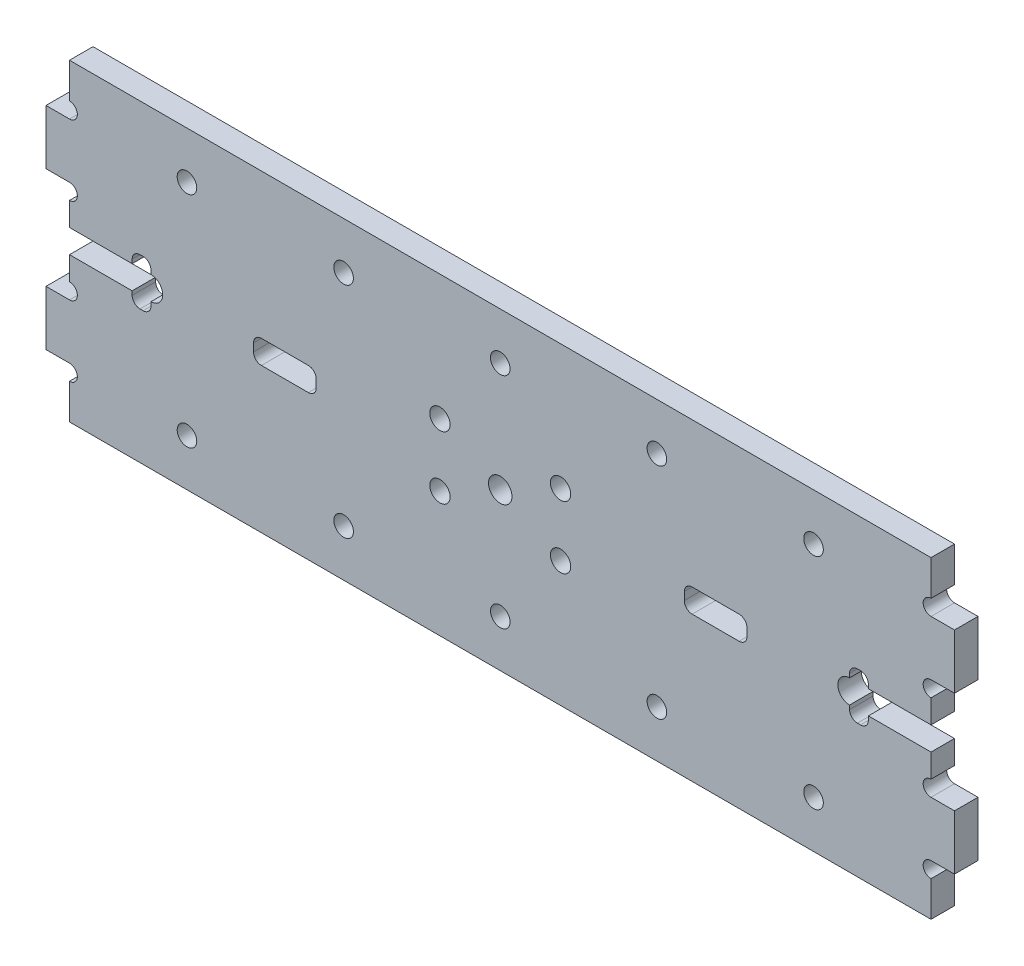
SolidWorks part; units mm, degrees
material "Acrylic (Medium-high impact)"
ref_plane "Front Plane" through (0, 0, 0) normal (0, 0, 1) x (1, 0, 0)
ref_plane "Top Plane" through (0, 0, 0) normal (0, 1, 0) x (1, 0, 0)
ref_plane "Right Plane" through (0, 0, 0) normal (1, 0, 0) x (0, 0, -1)
sketch "Sketch1" plane through (0, 0, 0) normal (0, 0, 1) x (1, 0, 0)
  line L0 (0, 20) -> (0, -20) construction
  line L1 (-55, 20) -> (55, 20)
  line L2 (-55, 20) -> (-55, -20)
  line L3 (-55, -20) -> (55, -20)
  line L4 (55, 20) -> (55, -20)
  line L5 (55, 0) -> (-55, 0) construction
  point P8 (0, 0)
extrude "Boss-Extrude1" add sketch "Sketch1" along normal blind 3
sketch "Sketch2" plane through (0, 0, 3) normal (0, 0, 1) x (1, 0, 0)
  line L0 (-55, 0) -> (55, 0) construction
  line L1 (-55, 20) -> (-55, -20) construction
  line L2 (55, -20) -> (55, 20) construction
  line L3 (55, 0) -> (55, -20) construction
  line L4 (55, 0) -> (55, 20) construction
  line L5 (55, 20) -> (58, 20) construction
  line L6 (58, 20) -> (58, -20) construction
  line L7 (58, -20) -> (55, -20) construction
  line L8 (0, 20) -> (0, -20) construction
  line L9 (55, 20) -> (-55, 20) construction
  line L10 (-55, -20) -> (55, -20) construction
  line L11 (55, -10) -> (58, -10) construction
  line L12 (55, 10) -> (58, 10) construction
  line L13 (58, 10) -> (58, 13.5)
  line L14 (58, 10) -> (58, 6.5)
  line L15 (58, 6.5) -> (55, 6.5)
  line L16 (55, 6.5) -> (55, 13.5)
  line L17 (55, 13.5) -> (58, 13.5)
  line L18 (55, -10) -> (55, -6.5)
  line L19 (55, -6.5) -> (58, -6.5)
  line L20 (58, -6.5) -> (58, -13.5)
  line L21 (58, -13.5) -> (55, -13.5)
  line L22 (55, -13.5) -> (55, -10)
  line L23 (-55, 6.5) -> (-55, 13.5)
  line L24 (-55, -13.5) -> (-55, -10)
  line L25 (-55, -10) -> (-55, -6.5)
  line L26 (-55, 10) -> (-58, 10) construction
  line L27 (-55, -10) -> (-58, -10) construction
  line L28 (-58, -20) -> (-55, -20) construction
  line L29 (-58, 20) -> (-58, -20) construction
  line L30 (-55, 20) -> (-58, 20) construction
  line L31 (-58, -13.5) -> (-55, -13.5)
  line L32 (-58, -6.5) -> (-58, -13.5)
  line L33 (-55, -6.5) -> (-58, -6.5)
  line L34 (-55, 13.5) -> (-58, 13.5)
  line L35 (-58, 6.5) -> (-55, 6.5)
  line L36 (-58, 10) -> (-58, 6.5)
  line L37 (-58, 10) -> (-58, 13.5)
extrude "Boss-Extrude2" add sketch "Sketch2" against normal blind 3
sketch "Sketch3" plane through (0, 0, 3) normal (0, 0, 1) x (1, 0, 0)
  line L0 (-55, 0) -> (55, 0) construction
  line L1 (-55, 6.5) -> (-55, -6.5) construction
  line L2 (55, -6.5) -> (55, 6.5) construction
  line L3 (-55, 13.5) -> (-55, 14.5) construction
  line L4 (-55, 20) -> (-55, 13.5) construction
  line L5 (-55, 14.5) -> (55, 14.5) construction
  line L6 (55, 13.5) -> (55, 20) construction
  line L7 (55, 14.5) -> (55, 5.5) construction
  line L8 (55, 5.5) -> (-55, 5.5) construction
  line L9 (-55, -6.5) -> (-55, -5.5) construction
  line L10 (-55, -5.5) -> (55, -5.5) construction
  line L11 (55, -5.5) -> (55, -14.5) construction
  line L12 (55, -20) -> (55, -13.5) construction
  line L13 (55, -14.5) -> (-55, -14.5) construction
  line L14 (-55, -13.5) -> (-55, -20) construction
  circle A0 centre (0, 0) radius 1.5
  circle A1 centre (-55, 14.5) radius 1
  circle A2 centre (-55, 5.5) radius 1
  circle A3 centre (-55, -5.5) radius 1
  circle A4 centre (-55, -14.5) radius 1
  circle A5 centre (55, 14.5) radius 1
  circle A6 centre (55, 5.5) radius 1
  circle A7 centre (55, -5.5) radius 1
  circle A8 centre (55, -14.5) radius 1
  line M2 (-55, 20) -> (-55, 13.5)
  line M6 (-55, 6.5) -> (-55, -6.5)
  line M10 (-55, -13.5) -> (-55, -20)
  line M12 (55, -20) -> (55, -13.5)
  line M16 (55, -6.5) -> (55, 6.5)
  line M20 (55, 13.5) -> (55, 20)
extrude "Cut-Extrude1" cut sketch "Sketch3" against normal blind 3 contours A4 M10 | A3 M6 | A2 M6 | A1 M2 | A0 | A7 M16 | A8 M12 | A6 M16 | A5 M20 region at (0, 0, 3) region at (-54.5756, 14.5, 3) region at (-54.5756, 5.5, 3) region at (-54.5756, -5.5, 3) region at (-54.5756, -14.5, 3) region at (54.5756, 14.5, 3) region at (54.5756, -5.5, 3) region at (54.5756, 5.5, 3) region at (54.5756, -14.5, 3)
sketch "Sketch4" plane through (0, 0, 3) normal (0, 0, 1) x (1, 0, 0)
  line L0 (-55, 0) -> (55, 0) construction
  line L1 (-55, 4.5) -> (-55, -4.5) construction
  line L2 (55, -4.5) -> (55, 4.5) construction
  line L3 (55, 0) -> (55, -1.5) construction
  line L4 (55, -1.5) -> (-55, -1.5) construction
  line L5 (-55, -1.5) -> (-55, 1.5) construction
  line L6 (-55, 1.5) -> (55, 1.5) construction
  line L7 (55, 1.5) -> (47, 1.5) construction
  line L8 (47, 20) -> (47, -20) construction
  line L9 (55, 20) -> (-55, 20) construction
  line L10 (-55, -20) -> (55, -20) construction
  line L11 (-55, 1.5) -> (-47, 1.5) construction
  line L12 (-47, 20) -> (-47, -20) construction
  line L13 (-47, 20) -> (-44.6, 20) construction
  line L14 (-44.6, 20) -> (-44.6, -20) construction
  line L15 (47, 20) -> (44.6, 20) construction
  line L16 (44.6, 20) -> (44.6, -20) construction
  line L17 (55, 1.5) -> (55, 3) construction
  line L18 (55, 3) -> (-55, 3) construction
  line L19 (-55, 3) -> (-55, -3) construction
  line L20 (-55, -3) -> (55, -3) construction
  line L21 (-44.6, 0) -> (-43.1, 0) construction
  line L22 (44.6, 0) -> (43.1, 0) construction
  line L24 (-55, 1.5) -> (-47, 1.5)
  line L25 (-55, 1.5) -> (-55, -1.5)
  line L26 (-55, -1.5) -> (-47, -1.5)
  line L27 (-47, 1.5) -> (-47, -1.5)
  line L28 (-47, 3) -> (-44.6, 3)
  line L29 (-47, 3) -> (-47, -3)
  line L30 (-47, -3) -> (-44.6, -3)
  line L31 (-44.6, 3) -> (-44.6, -3)
  line L32 (44.6, 3) -> (47, 3)
  line L33 (44.6, 3) -> (44.6, -3)
  line L34 (44.6, -3) -> (47, -3)
  line L35 (47, 3) -> (47, -3)
  line L36 (47, 1.5) -> (55, 1.5)
  line L37 (47, 1.5) -> (47, -1.5)
  line L38 (47, -1.5) -> (55, -1.5)
  line L39 (55, 1.5) -> (55, -1.5)
  arc A0 (44.6, 1.5) -> (44.6, -1.5) centre (44.6, 0) ccw
  arc A1 (-44.6, 1.5) -> (-44.6, -1.5) centre (-44.6, 0) cw
  line M10 (-55, 4.5) -> (-55, -4.5)
  line M24 (55, -4.5) -> (55, 4.5)
extrude "Cut-Extrude2" cut sketch "Sketch4" against normal blind 3 contours L27 L24 L26 M10 | L31 L28 L29 L27 L30 | A1 L31 | L35 L32 L33 L34 | L33 A0 | L35 L38 L36 M24 region at (-51, 0, 3) region at (-45.8, 0, 3) region at (-43.9634, 0, 3) region at (45.8, 0, 3) region at (43.9634, 0, 3) region at (51, 0, 3)
fillet "Fillet6" radius 1 8 edges at (-44.6, 3, 1.5) (-47, 3, 1.5) (-44.6, -3, 1.5) (-47, -3, 1.5) (47, 3, 1.5) (44.6, 3, 1.5) (47, -3, 1.5) (44.6, -3, 1.5)
sketch "Sketch5" plane through (0, 0, 3) normal (0, 0, 1) x (1, 0, 0)
  line L0 (-55, -1.5) -> (-55, 1.5) construction
  line L1 (55, -1.5) -> (55, 1.5) construction
  line L2 (-55, 0) -> (0, 0) construction
  line L3 (0, 0) -> (55, 0) construction
  line L4 (-27.5, 0) -> (-27.5, 1.5) construction
  line L5 (-27.5, 1.5) -> (-23.5, 1.5) construction
  line L6 (-23.5, 1.5) -> (-23.5, -1.5) construction
  line L7 (-23.5, -1.5) -> (-31.5, -1.5) construction
  line L8 (-31.5, -1.5) -> (-31.5, 1.5) construction
  line L9 (-31.5, 1.5) -> (-27.5, 1.5) construction
  line L10 (27.5, 0) -> (27.5, 1.5) construction
  line L11 (27.5, 1.5) -> (31.5, 1.5) construction
  line L12 (31.5, 1.5) -> (31.5, -1.5) construction
  line L13 (31.5, -1.5) -> (23.5, -1.5) construction
  line L14 (23.5, -1.5) -> (23.5, 1.5) construction
  line L15 (23.5, 1.5) -> (27.5, 1.5) construction
  line L17 (-31.5, 1.5) -> (-23.5, 1.5)
  line L18 (-31.5, 1.5) -> (-31.5, -1.5)
  line L19 (-31.5, -1.5) -> (-23.5, -1.5)
  line L20 (-23.5, 1.5) -> (-23.5, -1.5)
  line L21 (23.5, 1.5) -> (31.5, 1.5)
  line L22 (23.5, 1.5) -> (23.5, -1.5)
  line L23 (23.5, -1.5) -> (31.5, -1.5)
  line L24 (31.5, 1.5) -> (31.5, -1.5)
extrude "Cut-Extrude3" cut sketch "Sketch5" against normal blind 10
fillet "Fillet7" radius 1 8 edges at (-31.5, -1.5, 1.5) (-31.5, 1.5, 1.5) (-23.5, 1.5, 1.5) (23.5, -1.5, 1.5) (23.5, 1.5, 1.5) (31.5, 1.5, 1.5) (31.5, -1.5, 1.5) (-23.5, -1.5, 1.5)
sketch "Sketch6" plane through (0, 0, 3) normal (0, 0, 1) x (1, 0, 0)
  line L0 (0, 0) -> (0, 20) construction
  line L1 (55, 20) -> (-55, 20) construction
  line L2 (0, 20) -> (0, 14) construction
  line L3 (0, 0) -> (0, -20) construction
  line L4 (-55, -20) -> (55, -20) construction
  line L5 (0, -20) -> (0, -14) construction
  circle A0 centre (0, 14) radius 1.25
  circle A1 centre (0, -14) radius 1.25
  circle A2 centre (20, -14) radius 1.25
  circle A3 centre (20, 14) radius 1.25
  circle A4 centre (40, -14) radius 1.25
  circle A5 centre (40, 14) radius 1.25
  circle A6 centre (-20, -14) radius 1.25
  circle A7 centre (-20, 14) radius 1.25
  circle A8 centre (-40, -14) radius 1.25
  circle A9 centre (-40, 14) radius 1.25
  dimension "D1" = 3
  dimension "D2" = 3
extrude "Cut-Extrude4" cut sketch "Sketch6" against normal through all contours A8 | A6 | A1 | A2 | A4 | A5 | A3 | A0 | A7 | A9 region at (0, 14, 3) region at (0, -14, 3) region at (20, -14, 3) region at (20, 14, 3) region at (40, -14, 3) region at (40, 14, 3) region at (-20, -14, 3) region at (-20, 14, 3) region at (-40, -14, 3) region at (-40, 14, 3)
sketch "Sketch7" plane through (0, 0, 3) normal (0, 0, 1) x (1, 0, 0)
  line L0 (0, 0) -> (0, 4) construction
  line L1 (0, 4) -> (7.7, 4) construction
  line L2 (7.7, 4) -> (7.7, -4) construction
  line L3 (7.7, -4) -> (-7.7, -4) construction
  line L4 (-7.7, -4) -> (-7.7, 4) construction
  line L5 (-7.7, 4) -> (0, 4) construction
  circle A0 centre (-7.7, 4) radius 1.3
  circle A1 centre (7.7, 4) radius 1.3
  circle A2 centre (7.7, -4) radius 1.3
  circle A3 centre (-7.7, -4) radius 1.3
extrude "Cut-Extrude5" cut sketch "Sketch7" against normal blind 10
